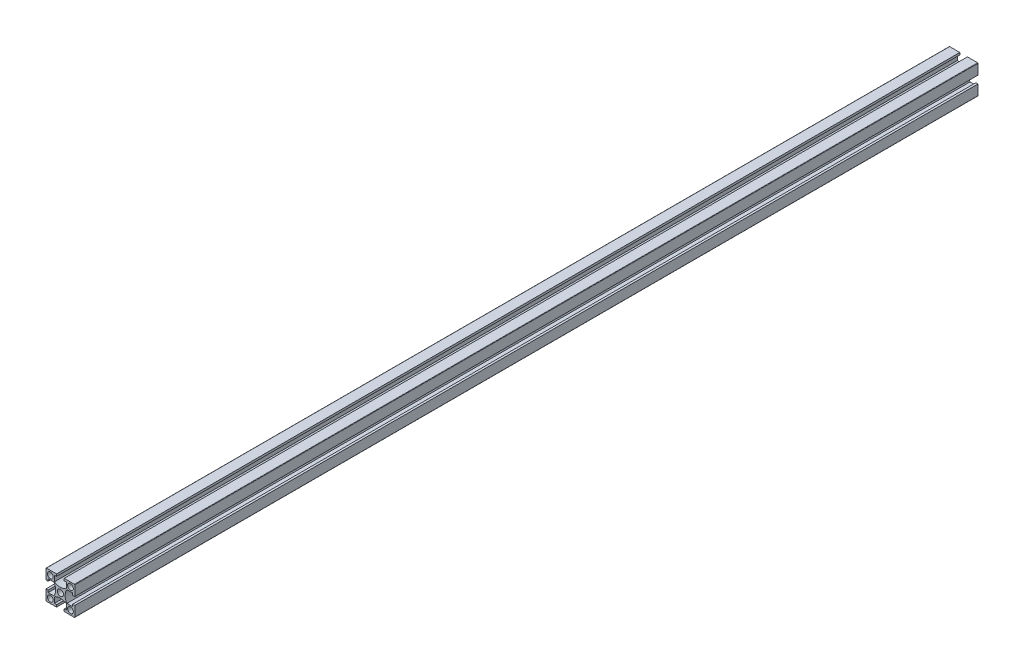
SolidWorks part; units mm, degrees
ref_plane "정면" through (0, 0, 0) normal (0, 0, 1) x (1, 0, 0)
ref_plane "윗면" through (0, 0, 0) normal (0, 1, 0) x (1, 0, 0)
ref_plane "우측면" through (0, 0, 0) normal (1, 0, 0) x (0, 0, -1)
sketch "스케치1" plane through (0, 0, 0) normal (0, 0, 1) x (1, 0, 0)
  line L0 (0, 32.0265) -> (0, -31.6588) construction
  line L1 (-10, 10) -> (-10, -10)
  line L2 (-10, 10) -> (10, 10)
  line L3 (-10, 2.65) -> (-8.5, 2.65)
  line L4 (13.6618, 0) -> (-11.6993, 0) construction
  line L5 (-8.5, 2.65) -> (-8.5, 4.15)
  line L6 (-8.5, 4.15) -> (-4.5032, 4.15)
  line L7 (-10, -2.65) -> (-8.5, -2.65)
  line L8 (-8.5, -2.65) -> (-8.5, -4.15)
  line L9 (-8.5, -4.15) -> (-4.5032, -4.15)
  line L10 (-10, -10) -> (10, -10)
  line L11 (10, 10) -> (10, -10)
  circle A0 centre (-7, 7) radius 2
  circle A1 centre (-7, -7) radius 2
  arc A2 (-4.5032, 4.15) -> (-4.5032, -4.15) centre (-11.0587, 0) cw
  circle A3 centre (0, 0) radius 2.15
  circle A4 centre (7, 7) radius 2
  circle A5 centre (7, -7) radius 2
  point P21 (-10, 0)
  point P23 (-3.3, 0)
  point P31 (0, -10)
  point P32 (0, 10)
  dimension "D3" = 4
  dimension "D9" = 6.7
  dimension "D10" = 4.3
  dimension "D11" = 7.7587
  dimension "D1" = 20
  dimension "D2" = 20
  dimension "D4" = 14
  dimension "D5" = 14
  dimension "D6" = 5.3
  dimension "D7" = 8.3
  dimension "D8" = 1.5
extrude "보스-돌출1" add sketch "스케치1" along normal blind 628 contours A0 | A4 | A3 | A5 | A1 | A2 L6 L5 L3 L1 L7 L8 L9 | L2 L11 L10 L1 region at (-6.6069, 0, 0) region at (-7, 7, 0) region at (-7, -7, 0) region at (0, 0, 0) region at (7, 7, 0) region at (7, -7, 0)
extrude "컷-돌출1" cut sketch "스케치1<3>" along normal up to next contours A2 L6 L5 L3 L1 L7 L8 L9 region at (-6.6069, 0, 0)
sketch "스케치1<3>" plane through (0, 0, 0) normal (0, 0, 1) x (1, 0, 0) same geometry as "스케치1"
pattern_circular "원형 패턴1" count 4 over 360 about axis through (0, 0, 628) along (0, 0, -1) of "컷-돌출1" reverse direction yes
fillet "필렛1" radius 0.3 4 edges at (10, -10, 314) (-10, -10, 314) (-10, 10, 314) (10, 10, 314)
sketch "스케치2" plane through (0, 0, 0) normal (1, 0, 0) x (0, 0, -1)
  line L2 (0, -2.65) -> (0, -9.7) construction
  circle A0 centre (-15, 0) radius 2.5
  dimension "D2" = 5
  dimension "D1" = 15
extrude "컷-돌출2" cut sketch "스케치2" against normal through all both and the other way through all
sketch "스케치3" plane through (0, -10, 0) normal (0, -1, 0) x (1, 0, 0)
  line L0 (9.7, 131) -> (-9.7, 131) construction
  line L1 (9.7, 0) -> (9.7, 628) construction
  line L2 (-9.7, 628) -> (-9.7, 0) construction
  line L3 (-9.7, 0) -> (-2.65, 0) construction
  line L4 (9.7, 367) -> (-9.7, 367) construction
  circle A0 centre (0, 141) radius 2.5
  circle A1 centre (0, 357) radius 2.5
  dimension "D1" = 141
  dimension "D4" = 10
  dimension "D2" = 131
  dimension "D3" = 236
extrude "컷-돌출3" cut sketch "스케치3" against normal through all
sketch "스케치4" plane through (0, -10, 0) normal (0, -1, 0) x (1, 0, 0)
  circle A0 centre (0, 249) radius 2.5
  circle A4 centre (0, 141) radius 2.5 construction
  dimension "D1" = 108
extrude "컷-돌출4" cut sketch "스케치4" against normal through all
sketch "스케치5" plane through (0, -10, 0) normal (0, -1, 0) x (1, 0, 0)
  line L0 (-9.7, 485) -> (9.7, 485) construction
  line L1 (-9.7, 628) -> (-9.7, 0) construction
  line L2 (9.7, 0) -> (9.7, 628) construction
  line L3 (-9.7, 433) -> (9.7, 433) construction
  line L4 (-9.7, 295) -> (9.7, 295) construction
  line L5 (-9.7, 248.9) -> (9.7, 248.9) construction
  line L6 (-9.7, 423) -> (9.7, 423) construction
  line L7 (-9.7, 196.9) -> (9.7, 196.9) construction
  line L8 (2.65, 628) -> (9.7, 628) construction
  line L9 (-9.7, 628) -> (-2.65, 628) construction
  line L10 (-9.7, 74.15) -> (9.7, 74.15) construction
  line L11 (-9.7, 2.15) -> (9.7, 2.15) construction
  line L12 (-9.7, 475) -> (9.7, 475) construction
  line L13 (-9.7, 305) -> (9.7, 305) construction
  line L14 (-9.7, 238.9) -> (9.7, 238.9) construction
  line L15 (-9.7, 186.9) -> (9.7, 186.9) construction
  line L16 (-9.7, 64.15) -> (9.7, 64.15) construction
  line L17 (-9.7, 12.15) -> (9.7, 12.15) construction
  circle A0 centre (0, 475) radius 2.15
  circle A2 centre (0, 423) radius 2.15
  circle A3 centre (0, 305) radius 2.12
  circle A4 centre (0, 238.9) radius 2.15
  circle A5 centre (0, 186.9) radius 2.15
  circle A6 centre (0, 64.15) radius 2.15
  circle A7 centre (0, 12.15) radius 2.15
  dimension "D15" = 4.3
  dimension "D1" = 143
  dimension "D2" = 195
  dimension "D3" = 333
  dimension "D4" = 379.1
  dimension "D5" = 431.1
  dimension "D6" = 553.85
  dimension "D7" = 625.85
  dimension "D8" = 10
  dimension "D9" = 10
  dimension "D10" = 10
  dimension "D11" = 10
  dimension "D12" = 10
  dimension "D13" = 10
  dimension "D14" = 10
extrude "컷-돌출5" cut sketch "스케치5" against normal through all
